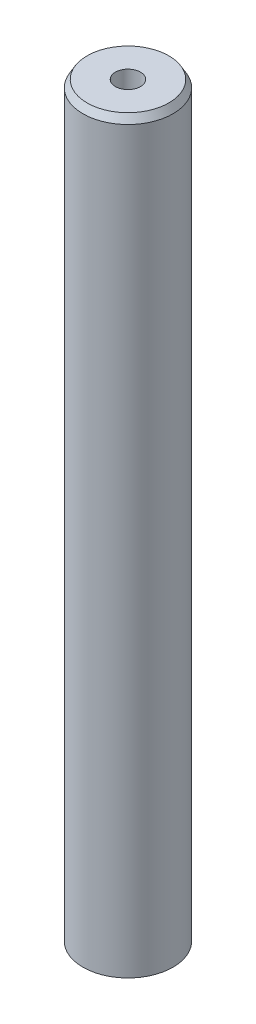
SolidWorks part; units mm, degrees
ref_plane "Front Plane" through (0, 0, 0) normal (0, 0, 1) x (1, 0, 0)
ref_plane "Top Plane" through (0, 0, 0) normal (0, 1, 0) x (1, 0, 0)
ref_plane "Right Plane" through (0, 0, 0) normal (1, 0, 0) x (0, 0, -1)
sketch "Sketch1" plane through (0, 0, 0) normal (0, 1, 0) x (1, 0, 0)
  circle A0 centre (0, 0) radius 7.5
  dimension "SHAFT_OD" = 15
extrude "Boss-Extrude1" add sketch "Sketch1" along normal blind 124.9263
sketch "Sketch2" plane through (0, 0, 0) normal (0, 1, 0) x (1, 0, 0)
  circle A0 centre (0, 0) radius 2.0901
  dimension "BORE_D" = 4.1802
extrude "Cut-Extrude1" cut sketch "Sketch2" along normal through all
chamfer "Chamfer1" distance 1.2115 angle 30 2 edges at (0, 124.9263, 7.5) (0, 0, 7.5) first distance on face at (0, 124.9263, 7.5) first distance on face at (0, 0, 2.0901)
